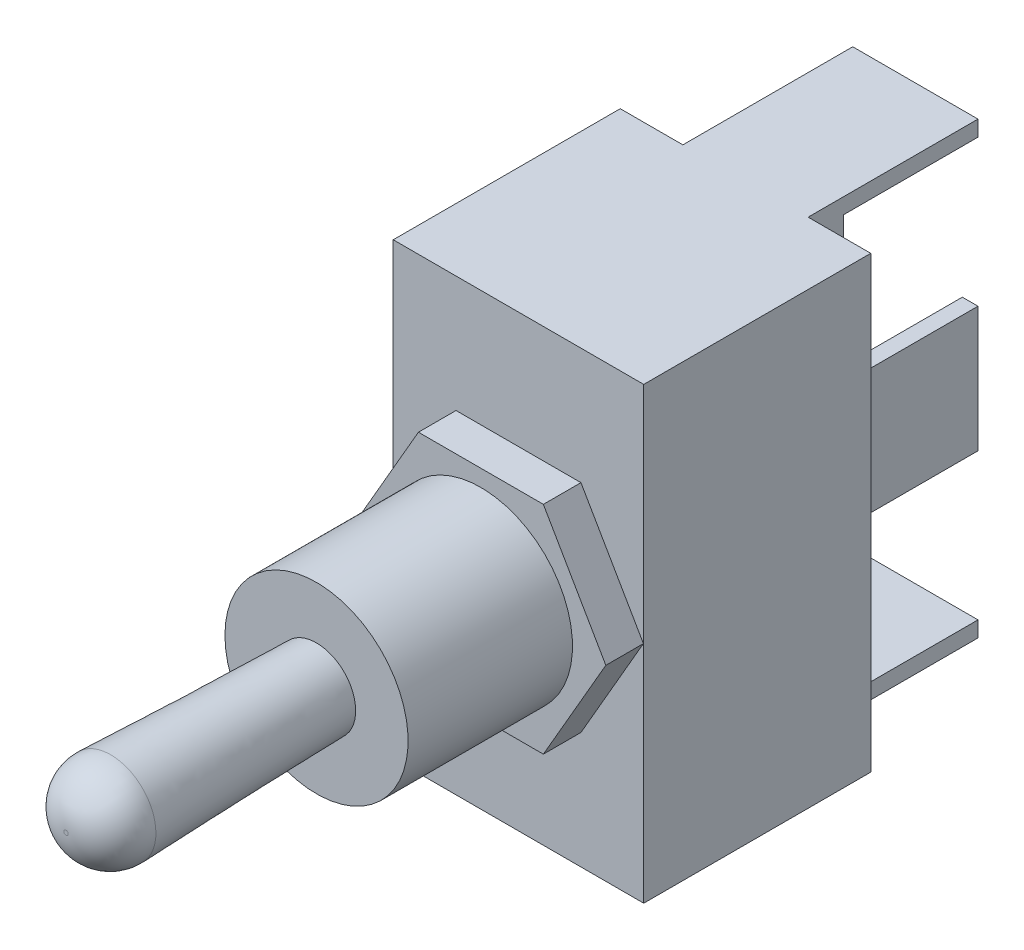
SolidWorks part; units mm, degrees
ref_plane "Front Plane" through (0, 0, 0) normal (0, 0, 1) x (1, 0, 0)
ref_plane "Top Plane" through (0, 0, 0) normal (0, 1, 0) x (1, 0, 0)
ref_plane "Right Plane" through (0, 0, 0) normal (1, 0, 0) x (0, 0, -1)
sketch "Sketch1" plane through (0, 0, 0) normal (0, 0, 1) x (1, 0, 0)
  line L1 (-8, -14.35) -> (8, -14.35)
  line L2 (-8, -14.35) -> (-8, 14.35)
  line L3 (-8, 14.35) -> (8, 14.35)
  line L4 (8, -14.35) -> (8, 14.35)
  line L5 (-8, -14.35) -> (8, 14.35) construction
  line L6 (-8, 14.35) -> (8, -14.35) construction
  point P0 (0, 0)
  dimension "D1" = 28.7
  dimension "D2" = 16
extrude "Boss-Extrude1" add sketch "Sketch1" along normal blind 14.5
sketch "Sketch2" plane through (0, 0, 14.5) normal (0, 0, 1) x (1, 0, 0)
  line L1 (-7.979, 0) -> (-3.9895, -6.91)
  line L2 (-3.9895, -6.91) -> (3.9895, -6.91)
  line L3 (3.9895, -6.91) -> (7.979, 0)
  line L4 (7.979, 0) -> (3.9895, 6.91)
  line L5 (3.9895, 6.91) -> (-3.9895, 6.91)
  line L6 (-3.9895, 6.91) -> (-7.979, 0)
  circle A0 centre (0, 0) radius 6.91 construction
  dimension "D1" = 13.82
extrude "Boss-Extrude2" add sketch "Sketch2" along normal blind 2.4
sketch "Sketch3" plane through (0, 0, 16.9) normal (0, 0, 1) x (1, 0, 0)
  circle A0 centre (0, 0) radius 5.85
  dimension "D1" = 11.7
extrude "Boss-Extrude3" add sketch "Sketch3" along normal blind 10.5
sketch "Sketch4" plane through (0, 0, 0) normal (0, 0, -1) x (-1, 0, 0)
  line L0 (-8, 14.35) -> (8, 14.35) construction
  line L1 (-4, -14.35) -> (4, -14.35)
  line L2 (-4, -14.35) -> (-4, 14.35)
  line L3 (-4, 14.35) -> (4, 14.35)
  line L4 (4, -14.35) -> (4, 14.35)
  line L5 (-4, -14.35) -> (4, 14.35) construction
  line L6 (-4, 14.35) -> (4, -14.35) construction
  point P0 (0, 0)
  dimension "D1" = 8
extrude "Boss-Extrude4" add sketch "Sketch4" along normal blind 2.25
sketch "Sketch5" plane through (0, 0, 27.4) normal (0, 0, 1) x (1, 0, 0)
  circle A0 centre (0, 0) radius 2.5
  dimension "D1" = 5
ref_plane "Plane1" through (0, 0, 43.4) normal (0, 0, 1) x (1, 0, 0)
sketch "Sketch6" plane through (0, 0, 43.4) normal (0, 0, 1) x (1, 0, 0)
  circle A0 centre (0, 0) radius 3
  dimension "D1" = 6
loft "Loft1" add profiles "Sketch5", "Sketch6" connector at (2.468, 0.3988, 27.4) connector at (2.9569, -0.5065, 43.4)
fillet "Fillet3" radius 2.75 1 edges at (3, 0, 43.4)
sketch "Sketch7" plane through (0, 0, -2.25) normal (0, 0, -1) x (-1, 0, 0)
  line L0 (4, -14.35) -> (4, 14.35) construction
  line L1 (-4, 14.35) -> (4, 14.35)
  line L2 (-4, 14.35) -> (-4, 13.35)
  line L3 (-4, 13.35) -> (4, 13.35)
  line L4 (4, 14.35) -> (4, 13.35)
  line L5 (-4, 14.35) -> (-4, -14.35) construction
  line L6 (-4, -14.35) -> (4, -14.35)
  line L7 (-4, -14.35) -> (-4, -13.35)
  line L8 (-4, -13.35) -> (4, -13.35)
  line L9 (4, -14.35) -> (4, -13.35)
  line L10 (-4, 4) -> (-3, 4)
  line L11 (-4, 4) -> (-4, -4)
  line L12 (-4, -4) -> (-3, -4)
  line L13 (-3, 4) -> (-3, -4)
  point P18 (-3, 0)
  dimension "D1" = 1
extrude "Boss-Extrude5" add sketch "Sketch7" along normal blind 8.6
